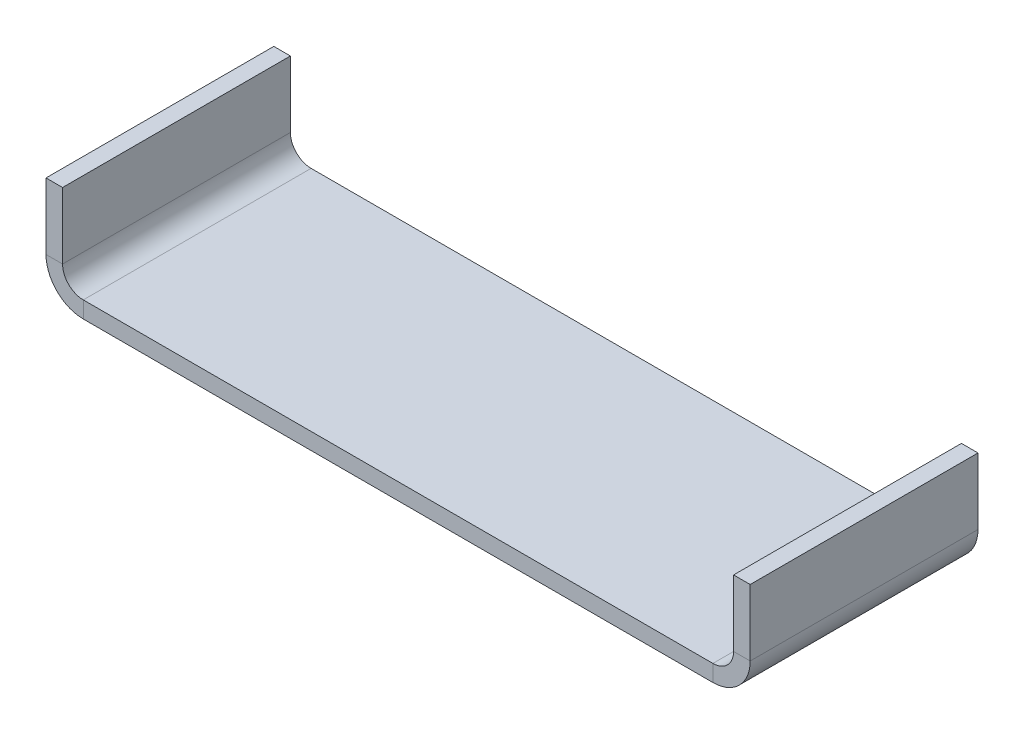
SolidWorks part; units mm, degrees
note: The reader was unsure of these and kept them because the rebuilt part matched: thickness of "Base-Flange1"; flange length of "Edge-Flange1".
material "Plain Carbon Steel"
ref_plane "Front Plane" through (0, 0, 0) normal (0, 0, 1) x (1, 0, 0)
ref_plane "Top Plane" through (0, 0, 0) normal (0, 1, 0) x (1, 0, 0)
ref_plane "Right Plane" through (0, 0, 0) normal (1, 0, 0) x (0, 0, -1)
sketch "Sketch1" plane through (0, 0, 0) normal (0, 0, 1) x (1, 0, 0)
  arc A0 (-100.5, -0.0622) -> (-100.5, 0.0622) centre (0, 0) ccw
  dimension "D1" = 100.5
sketch "Sketch2" plane through (0, 0, 0) normal (0, 1, 0) x (1, 0, 0)
  line L1 (-85, -55) -> (85, -55)
  line L2 (-85, -55) -> (-85, 55)
  line L3 (-85, 55) -> (85, 55)
  line L4 (85, -55) -> (85, 55)
  line L5 (-85, -55) -> (85, 55) construction
  line L6 (-85, 55) -> (85, -55) construction
  point P0 (0, 0)
  dimension "D1" = 170
  dimension "D2" = 110
base flange "Base-Flange1" sketch "Sketch2" thickness 8 reverse thickness direction no parameters "D1"=15
edge flange "Edge-Flange1" sketch "Sketch7" flange angle 90 flange length 50 flange position material inside bend radius 10 thickness 8 relief rectangular parameters "D6"=10
sketch "Sketch7" plane through (85, 0, 0) normal (1, 0, 0) x (0, 0, -1)
  line L2 (-55, 0) -> (-55, 42)
  line L3 (-55, 42) -> (55, 42)
  line L4 (55, 42) -> (55, 0)
  line L7 (-55, 0) -> (55, 0) construction
  line L8 (-55, 0) -> (55, 0)
bend "EdgeBend1" bend radius 10 bend angle 90 parameters "D5"=1
mirror "Mirror1" about plane through (-85, -8, 55) normal (-1, 0, 0) of bodies 106
bend "MirrorBend1" bend radius 10 bend angle 90 parameters "D5"=2
sketch "Bend-Lines3" [suppressed] plane through (0, 0, 0) normal (0, 1, 0) x (1, 0, 0)
sketch "Bounding-Box3" [suppressed] plane through (0, 0, 0) normal (0, 1, 0) x (1, 0, 0)
sheet metal parameters "Sheet-Metal5" thickness 8 parameters "D1"=15
flat pattern "Flat-Pattern5" [suppressed]
sketch "Bend-Lines4" plane through (0, 0, 0) normal (0, 1, 0) x (1, 0, 0)
sketch3d "Bounding-Box4" [suppressed]
  line L0 (-75, 50, 0) -> (75, 50, 0) construction
  line L1 (-75, -50, 0) -> (75, -50, 0) construction
  line L2 (-75, 50, 0) -> (-75, -50, 0) construction
  line L3 (75, 50, 0) -> (75, -50, 0) construction
sheet metal parameters "Sheet-Metal6" thickness 8 parameters "D1"=15
flat pattern "Flat-Pattern5"
sketch "Bend-Lines4" plane through (0, 0, 0) normal (0, 1, 0) x (1, 0, 0)
  line L0 (47.9956, -47) -> (47.9956, 47) construction
  line L1 (47.9956, -47) -> (47.9956, 47) construction
sketch3d "Bounding-Box4" [suppressed]
  line L0 (100.9911, 47, 0) -> (-55, 47, 0) construction
  line L1 (100.9911, -47, 0) -> (-55, -47, 0) construction
  line L2 (100.9911, 47, 0) -> (100.9911, -47, 0) construction
  line L3 (-55, 47, 0) -> (-55, -47, 0) construction
bend of the flat pattern "Flatten-<EdgeBend1>1"
sheet metal parameters "Sheet-Metal7" thickness 8 parameters "D1"=15
flat pattern "Flat-Pattern7"
sketch "Bend-Lines5" plane through (0, 0, 0) normal (0, 1, 0) x (1, 0, 0)
  line L0 (-247.9956, 55) -> (-247.9956, -55) construction
  line L1 (77.9956, -55) -> (77.9956, 55) construction
  line L2 (-247.9956, 55) -> (-247.9956, -55) construction
  line L3 (77.9956, -55) -> (77.9956, 55) construction
sketch3d "Bounding-Box5" [suppressed]
  line L0 (120.9911, 55, 0) -> (-290.9911, 55, 0) construction
  line L1 (120.9911, -55, 0) -> (-290.9911, -55, 0) construction
  line L2 (120.9911, 55, 0) -> (120.9911, -55, 0) construction
  line L3 (-290.9911, 55, 0) -> (-290.9911, -55, 0) construction
bend of the flat pattern "Flatten-<EdgeBend1>2"
bend of the flat pattern "Flatten-<MirrorBend1>1"
